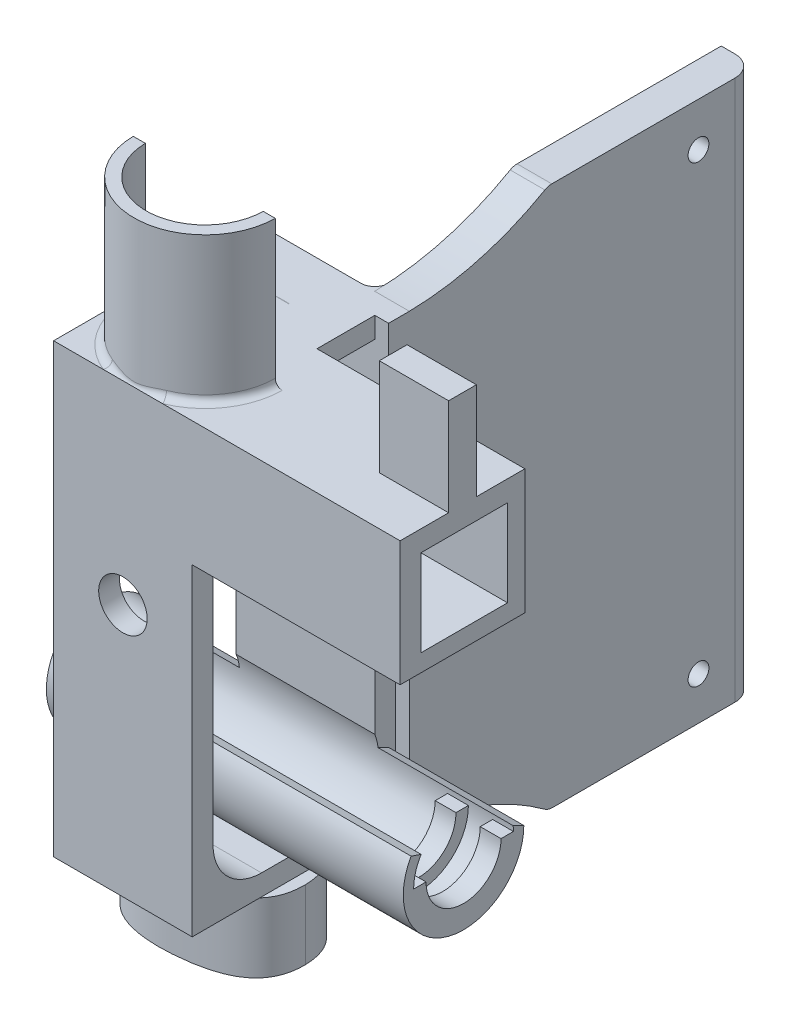
SolidWorks part; units mm, degrees
ref_plane "Front Plane" through (0, 0, 0) normal (0, 0, 1) x (1, 0, 0)
ref_plane "Top Plane" through (0, 0, 0) normal (0, 1, 0) x (1, 0, 0)
ref_plane "Right Plane" through (0, 0, 0) normal (1, 0, 0) x (0, 0, -1)
sketch "Sketch1" plane through (0, 0, 0) normal (1, 0, 0) x (0, 0, -1)
  line L26 (-11.675, 29.25) -> (11.675, 29.25)
  line L27 (-11.675, 29.25) -> (-11.675, -29.25)
  line L28 (-11.675, -29.25) -> (11.675, -29.25)
  line L29 (11.675, 29.25) -> (11.675, -29.25)
  line L30 (-11.675, 29.25) -> (11.675, -29.25) construction
  line L31 (-11.675, -29.25) -> (11.675, 29.25) construction
  line L32 (-14.675, 32.25) -> (14.675, 32.25)
  line L33 (-14.675, 32.25) -> (-14.675, -32.25)
  line L34 (-14.675, -32.25) -> (14.675, -32.25)
  line L35 (14.675, 32.25) -> (14.675, -32.25)
  line L36 (-14.675, 32.25) -> (14.675, -32.25) construction
  line L37 (-14.675, -32.25) -> (14.675, 32.25) construction
  point P0 (0, 0)
  point P5 (0, 0)
  dimension "D1" = 3
  dimension "D2" = 3
  dimension "D3" = 64.5
  dimension "D4" = 29.35
extrude "Boss-Extrude2" add sketch "Sketch1" along normal mid plane 20
sketch "Sketch3" plane through (0, 0, -14.675) normal (0, 0, -1) x (-1, 0, 0)
  line L0 (0, 32.25) -> (0, -32.25) construction
  line L1 (-10, 32.25) -> (10, 32.25) construction
  line L2 (-10, -32.25) -> (10, -32.25) construction
  circle A0 centre (0, 4.25) radius 3.5
  dimension "D1" = 7
  dimension "D2" = 36.5
extrude "Cut-Extrude2" cut sketch "Sketch3" against normal blind 44
sketch "Sketch6" plane through (10, 0, 0) normal (1, 0, 0) x (0, 0, -1)
  line L1 (12.1363, -22.004) -> (13.675, -22.75)
  line L2 (-14.675, -32.25) -> (14.675, -32.25) construction
  line L3 (-2.5895, -18.4526) -> (-1.1422, -18.9526)
  line L4 (11.675, -29.25) -> (11.675, 29.25) construction
  arc A0 (-2.5895, -18.4526) -> (13.675, -22.75) centre (4.975, -22.75) ccw
  arc A1 (-1.1422, -18.9526) -> (12.1363, -22.004) centre (4.975, -22.75) ccw
  dimension "D1" = 14.4
  dimension "D2" = 17.4
  dimension "D3" = 9.5
  dimension "D4" = 6.7
extrude "Boss-Extrude6" add sketch "Sketch6" along normal blind 19.5 and the other way blind 32
sketch "Sketch7" plane through (10, 0, 0) normal (1, 0, 0) x (0, 0, -1)
  line L1 (8.0718, -29.25) -> (1.8782, -29.25)
  line L2 (8.0718, -29.25) -> (1.8782, -29.25)
  arc A1 (1.8782, -29.25) -> (8.0718, -29.25) centre (4.975, -22.75) ccw
  arc A2 (1.8782, -29.25) -> (8.0718, -29.25) centre (4.975, -22.75) ccw
  dimension "D1" = 0
extrude "Cut-Extrude4" cut sketch "Sketch7" against normal blind 22
sketch "Sketch8" plane through (-22, 0, 0) normal (-1, 0, 0) x (0, 0, 1)
  line L0 (-13.675, -22.75) -> (1.1422, -18.9526)
  line L1 (1.1422, -18.9526) -> (2.5895, -18.4526)
  line L2 (-12.1363, -22.004) -> (-13.675, -22.75)
  line L3 (2.5895, -18.4526) -> (1.1422, -18.9526)
  arc A2 (-12.1363, -22.004) -> (1.1422, -18.9526) centre (-4.975, -22.75) ccw
  arc A3 (-13.675, -22.75) -> (2.5895, -18.4526) centre (-4.975, -22.75) ccw
  arc A5 (-13.675, -22.75) -> (2.5895, -18.4526) centre (-4.975, -22.75) ccw
  dimension "D1" = 0
extrude "Boss-Extrude7" add sketch "Sketch8" against normal blind 2
sketch "Sketch9" plane through (-22, 0, 0) normal (-1, 0, 0) x (0, 0, 1)
  circle A0 centre (-4.975, -22.75) radius 7
  circle A1 centre (-4.975, -22.75) radius 5
  dimension "D1" = 10
  dimension "D2" = 14
extrude "Boss-Extrude8" add sketch "Sketch9" against normal blind 7
sketch "Sketch10" plane through (-22, 0, 0) normal (-1, 0, 0) x (0, 0, 1)
  line L0 (-1.143, -19.5382) -> (-9.8795, -21.7773) construction
  line L1 (-1.143, -19.5382) -> (-9.8795, -21.7773)
  arc A0 (-1.143, -19.5382) -> (-9.8795, -21.7773) centre (-4.975, -22.75) ccw construction
  arc A1 (-1.143, -19.5382) -> (-9.8795, -21.7773) centre (-4.975, -22.75) ccw
extrude "Boss-Extrude9" add sketch "Sketch10" against normal blind 2
sketch "Sketch13" plane through (10, 0, 0) normal (1, 0, 0) x (0, 0, -1)
  line L1 (-14.675, 32.25) -> (3.325, 32.25)
  line L2 (-14.675, 32.25) -> (-14.675, 14.25)
  line L3 (-14.675, 14.25) -> (3.325, 14.25)
  line L4 (3.325, 32.25) -> (3.325, 14.25)
  line L5 (-11.675, 29.25) -> (0.825, 29.25)
  line L6 (-11.675, 29.25) -> (-11.675, 16.75)
  line L7 (-11.675, 16.75) -> (0.825, 16.75)
  line L8 (0.825, 29.25) -> (0.825, 16.75)
  dimension "D1" = 2.5
  dimension "D2" = 2.5
  dimension "D3" = 18
  dimension "D4" = 18
extrude "Boss-Extrude11" add sketch "Sketch13" along normal blind 50
sketch "Sketch14" plane through (10, 0, 0) normal (1, 0, 0) x (0, 0, -1)
  line L0 (3.325, 32.25) -> (-14.675, 32.25) construction
  line L1 (-14.675, 32.25) -> (-14.675, 14.25) construction
  line L2 (-11.675, 29.25) -> (-11.675, 16.75) construction
  line L3 (0.825, 29.25) -> (-11.675, 29.25) construction
  line L4 (0.825, 16.75) -> (0.825, 29.25) construction
  line L5 (-11.675, 16.75) -> (0.825, 16.75) construction
  line L6 (-14.675, 14.25) -> (3.325, 14.25) construction
  line L7 (3.325, 14.25) -> (3.325, 32.25) construction
  line L8 (3.325, 32.25) -> (-14.675, 32.25) construction
  line L9 (-14.675, 32.25) -> (-14.675, 14.25) construction
  line L10 (-11.675, 29.25) -> (-11.675, 16.75) construction
  line L11 (0.825, 29.25) -> (-11.675, 29.25) construction
  line L12 (0.825, 16.75) -> (0.825, 29.25) construction
  line L13 (-11.675, 16.75) -> (0.825, 16.75) construction
  line L14 (-14.675, 14.25) -> (3.325, 14.25) construction
  line L15 (3.325, 14.25) -> (3.325, 32.25) construction
  line L17 (3.325, 14.25) -> (-11.675, 14.25)
  line L18 (3.325, 14.25) -> (3.325, 29.25)
  line L19 (3.325, 29.25) -> (-11.675, 29.25)
  line L20 (-11.675, 14.25) -> (-11.675, 29.25)
extrude "Cut-Extrude5" cut sketch "Sketch14" against normal blind 32 and the other way blind 12
sketch "Sketch15" plane through (0, 32.25, 0) normal (0, 1, 0) x (1, 0, 0)
  line L0 (-9.9995, -4.2749) -> (-9.9995, -12.2749) construction
  line L2 (-10, -14.675) -> (-10, -12.275) construction
  line L4 (-10, 14.675) -> (-10, -14.675) construction
  arc A0 (-6.5495, -4.2749) -> (9.4505, -4.2749) centre (1.4505, -4.2749) ccw construction
  circle A1 centre (1.4505, -4.2749) radius 8.5
  circle A2 centre (1.4505, -4.2749) radius 10.25
  dimension "D3" = 20.5
  dimension "D2" = 17
  dimension "D1" = 2.4
sketch "Sketch17" plane through (10, 0, 0) normal (1, 0, 0) x (0, 0, -1)
  line L0 (-3.725, -22.75) -> (-0.435, -22.75)
  line L1 (10.385, -22.75) -> (13.675, -22.75)
  arc A0 (-3.725, -22.75) -> (13.675, -22.75) centre (4.975, -22.75) ccw
  arc A1 (-0.435, -22.75) -> (10.385, -22.75) centre (4.975, -22.75) ccw
  arc A2 (-2.5895, -18.4526) -> (13.675, -22.75) centre (4.975, -22.75) ccw construction
  dimension "D1" = 10.82
extrude "Boss-Extrude13" add sketch "Sketch17" along normal blind 3 from offset 10
sketch "Sketch18" plane through (23, 0, 0) normal (1, 0, 0) x (0, 0, -1)
  line L0 (29.8715, 26.1597) -> (33.1615, 26.1597) construction
  line L1 (43.9815, 26.1597) -> (47.2715, 26.1597) construction
  line L4 (-0.435, -22.75) -> (-2.225, -22.75)
  line L5 (12.175, -22.75) -> (10.385, -22.75)
  line L6 (-0.435, -22.75) -> (-2.225, -22.75)
  line L7 (12.175, -22.75) -> (10.385, -22.75)
  arc A0 (29.8715, 26.1597) -> (47.2715, 26.1597) centre (38.5715, 26.1597) ccw construction
  arc A1 (33.1615, 26.1597) -> (43.9815, 26.1597) centre (38.5715, 26.1597) ccw construction
  arc A4 (-2.225, -22.75) -> (12.175, -22.75) centre (4.975, -22.75) ccw
  arc A5 (-0.435, -22.75) -> (10.385, -22.75) centre (4.975, -22.75) ccw
  arc A6 (-2.225, -22.75) -> (12.175, -22.75) centre (4.975, -22.75) ccw
  arc A7 (-0.435, -22.75) -> (10.385, -22.75) centre (4.975, -22.75) ccw
  dimension "D1" = 10.82
  dimension "D2" = 0
extrude "Boss-Extrude14" add sketch "Sketch18" along normal blind 3 from offset 3.5
sketch "Sketch19" plane through (10, 0, 0) normal (1, 0, 0) x (0, 0, -1)
  circle A0 centre (4.975, -22.75) radius 7.2
  arc A2 (12.175, -22.75) -> (12.1363, -22.004) centre (4.975, -22.75) ccw construction
extrude "Cut-Extrude8" cut sketch "Sketch19" against normal blind 23
ref_plane "Plane1" through (29.5, 0, 0) normal (1, 0, 0) x (0, 0, -1)
sketch "Sketch20" plane through (0, -32.25, 0) normal (0, -1, 0) x (1, 0, 0)
  spline S0 degree 3 poles (11.6414, 0) (11.6674, 1.6037) (10.9896, 4.1961) (8.7731, 6.1964) (6.4516, 7.2309) (4.5046, 7.769) (2.42, 8.1116) (0.2664, 8.3123) (-1.8893, 8.3523) (-4.6777, 8.1275) (-7.8357, 7.2232) (-10.5686, 4.8022) (-11.3311, 2.0728) (-11.3586, 0.373) knots 0 0 0 0 0.125 0.25 0.3125 0.375 0.4375 0.5 0.5625 0.625 0.75 0.875 1 1 1 1 weights 1 1 1 1 1 1 1 1 1 1 1 1 1 1
  spline S1 degree 3 poles (-11.3586, 0.373) (-11.3862, -1.3268) (-10.7127, -4.0794) (-8.0597, -6.5878) (-4.9327, -7.594) (-2.1531, -7.9091) (0.0028, -7.939) (2.1618, -7.8083) (4.2564, -7.5335) (6.2198, -7.0588) (8.5736, -6.1002) (10.8538, -4.1728) (11.6154, -1.6037) (11.6414, 0) knots 0 0 0 0 0.125 0.25 0.375 0.4375 0.5 0.5625 0.625 0.6875 0.75 0.875 1 1 1 1 weights 1 1 1 1 1 1 1 1 1 1 1 1 1 1
extrude "Boss-Extrude16" add sketch "Sketch20" along normal blind 10 contours S1 S0
sketch "Sketch23" plane through (0, -42.25, 0) normal (0, -1, 0) x (1, 0, 0)
  ellipse E0 centre (0.5631, 0) end of major axis (8.837, 0) minor radius 5.0514
extrude "Cut-Extrude10" cut sketch "Sketch23" against normal up to surface (7 mm away) from offset 3 up to face at (2.5, -32.25, -7.1444) offset against normal yes
sketch "Sketch25" plane through (60, 0, 0) normal (1, 0, 0) x (0, 0, -1)
  line L0 (3.325, 32.25) -> (-14.675, 32.25) construction
  line L1 (-7.675, 46.25) -> (-3.675, 46.25)
  line L2 (-7.675, 46.25) -> (-7.675, 32.25)
  line L3 (-7.675, 32.25) -> (-3.675, 32.25)
  line L4 (-3.675, 46.25) -> (-3.675, 32.25)
  point P6 (-5.675, 32.25)
  point P7 (-5.675, 32.25)
  dimension "D1" = 4
  dimension "D2" = 14
extrude "Boss-Extrude17" add sketch "Sketch25" against normal blind 30
sketch "Sketch26" plane through (0, 0, -14.675) normal (0, 0, -1) x (-1, 0, 0)
  line L1 (-6.9844, 37.8983) -> (-11.9844, 37.8983)
  line L2 (-6.9844, 37.8983) -> (-6.9844, -40.1017)
  line L3 (-6.9844, -40.1017) -> (-11.9844, -40.1017)
  line L4 (-11.9844, 37.8983) -> (-11.9844, -40.1017)
  dimension "D1" = 78
  dimension "D2" = 5
extrude "Boss-Extrude18" add sketch "Sketch26" along normal blind 50
sketch "Sketch27" plane through (0, 0, -14.675) normal (0, 0, 1) x (1, 0, 0)
  line L0 (11.9844, 37.8983) -> (11.9844, -40.1017) construction
  line L1 (10, 32.25) -> (11.9844, 32.25)
  line L2 (10, 32.25) -> (10, -11.5734)
  line L3 (10, -11.5734) -> (11.9844, -11.5734)
  line L4 (11.9844, 32.25) -> (11.9844, -11.5734)
extrude "Boss-Extrude19" add sketch "Sketch27" along normal blind 3
fillet "Fillet1" radius 2 1 edges at (6.9844, 0, -14.675)
sketch "Sketch28" plane through (11.9844, 0, 0) normal (1, 0, 0) x (0, 0, -1)
  line L0 (64.675, 37.8983) -> (64.675, -40.1017) construction
  circle A0 centre (56.395, 31.5786) radius 1.5
  circle A1 centre (56.395, -33.9214) radius 1.5
  point P6 (0, 0)
  dimension "D3" = 3
  dimension "D1" = 8.28
  dimension "D2" = 65.5
extrude "Cut-Extrude11" cut sketch "Sketch28" against normal blind 13
fillet "Fillet2" radius 3 1 edges at (11.9844, -1.1017, -64.675)
fillet "Fillet3" radius 7 1 edges at (0, -29.25, 11.675)
extrude "Boss-Extrude20" add sketch "Sketch15" along normal blind 21
sketch "Sketch29" plane through (0, 32.25, 0) normal (0, 1, 0) x (1, 0, 0)
  line L1 (-10.1695, -4.384) -> (13.2997, -4.384)
  line L2 (-10.1695, -4.384) -> (-10.1695, 6.8976)
  line L3 (-10.1695, 6.8976) -> (13.2997, 6.8976)
  line L4 (13.2997, -4.384) -> (13.2997, 6.8976)
fillet "Fillet4" radius 1 1 edges at (1.4505, 32.25, -5.9751)
sketch "Sketch30" plane through (11.9844, 0, 0) normal (1, 0, 0) x (0, 0, -1)
  line L0 (61.675, 37.8983) -> (14.675, 37.8983) construction
  line L1 (14.675, -11.5734) -> (14.675, -40.1017) construction
  line L2 (61.675, -40.1017) -> (14.675, -40.1017) construction
  line L3 (34.6834, 37.8983) -> (14.675, 37.8983)
  line L4 (14.675, 37.8983) -> (14.675, 32.25)
  line L5 (34.6834, -40.1017) -> (14.675, -40.1017)
  line L6 (14.675, -40.1017) -> (14.675, -32.1478)
  arc A0 (14.675, 32.25) -> (34.6834, 37.8983) centre (13.9858, 72.9536) ccw
  arc A1 (14.675, -32.1478) -> (34.6834, -40.1017) centre (10.1761, -72.6079) cw
  point P12 (31.5834, -40.1017)
  point P15 (34.6834, -40.1017)
extrude "Cut-Extrude13" cut sketch "Sketch30" against normal blind 9
fillet "Fillet5" radius 2 2 edges at (9.4844, 37.8983, -34.6834) (9.4844, -40.1017, -34.6834)
sketch "Sketch31" plane through (60, 0, 0) normal (1, 0, 0) x (0, 0, -1)
  line L1 (9.3491, 8.0588) -> (-19.8354, 8.0588)
  line L2 (9.3491, 8.0588) -> (9.3491, 52.1818)
  line L3 (9.3491, 52.1818) -> (-19.8354, 52.1818)
  line L4 (-19.8354, 8.0588) -> (-19.8354, 52.1818)
extrude "Cut-Extrude14" cut sketch "Sketch31" against normal blind 20
extrude "Cut-Extrude15" cut sketch "Sketch29" along normal blind 25
